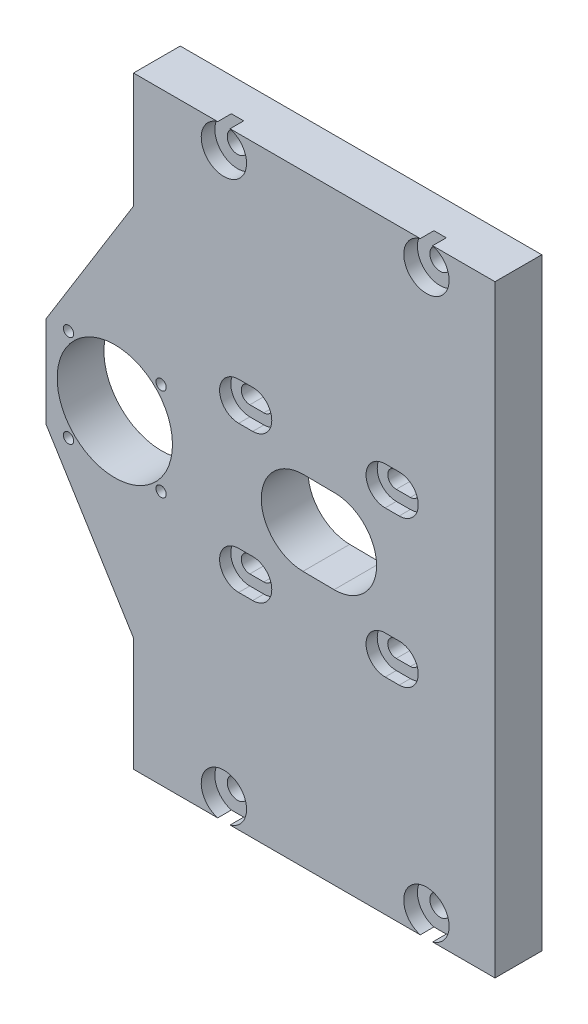
SolidWorks part; units mm, degrees
ref_plane "Front Plane" through (0, 0, 0) normal (0, 0, 1) x (1, 0, 0)
ref_plane "Top Plane" through (0, 0, 0) normal (0, 1, 0) x (1, 0, 0)
ref_plane "Right Plane" through (0, 0, 0) normal (1, 0, 0) x (0, 0, -1)
sketch "Sketch1" plane through (0, 0, 0) normal (0, 0, 1) x (1, 0, 0)
  line L24 (-148, 255) -> (-148, 190) construction
  line L31 (-148, 70) -> (-148, 10) construction
  line L32 (-148, 33.5) -> (-32, 33.5) construction
  line L36 (-32, 227) -> (-148, 227) construction
  line L37 (-148, 227) -> (-148, 190)
  line L38 (-148, 70) -> (-148, 33.5)
  line L39 (-148, 33.5) -> (-32, 33.5)
  line L43 (-32, 227) -> (-148, 227)
  line L44 (-176, 115.2267) -> (-176, 144.7733) construction
  line L45 (-176, 115.2267) -> (-176, 144.7733)
  line L46 (-176, 144.7733) -> (-148, 190)
  line L47 (-176, 115.2267) -> (-148, 70)
  line L51 (-32, 33.5) -> (-32, 227)
  circle A8 centre (-154, 130) radius 18.5
  circle A9 centre (-154, 130) radius 18.5
  dimension "D1" = 0.5
extrude "Boss-Extrude1" add sketch "Sketch1" along normal blind 15
sketch "Sketch2" plane through (0, 0, 15) normal (0, 0, 1) x (1, 0, 0)
  circle A1 centre (-139.1508, 115.1508) radius 2.25
  circle A3 centre (-168.8492, 115.1508) radius 2.25
  circle A5 centre (-168.8492, 144.8492) radius 2.25
  circle A7 centre (-139.1508, 144.8492) radius 2.25
hole_wizard "M4x0.7 Tapped Hole1" positions "Sketch3" profile "Sketch4" tap size "M4x0.7" standard "ANSI Metric"
sketch "Sketch3" plane through (0, 0, 15) normal (0, 0, 1) x (1, 0, 0)
  point P0 (-168.8492, 144.8492)
  point P3 (-139.1508, 144.8492)
  point P6 (-139.1508, 115.1508)
  point P9 (-168.8492, 115.1508)
sketch "Sketch4" plane through (-168.8492, 144.8492, 15) normal (1, 0, 0) x (0, -1, 0)
  line L0 (0, 0) -> (0, 14.1)
  line L1 (0, 14.1) -> (1.65, 13.1086)
  line L2 (1.65, 13.1086) -> (1.65, 0)
  line L5 (1.65, 0) -> (0, 0)
  line L10 (0, 14.1) -> (-1.65, 13.1086) construction
  line L11 (0, -6.35) -> (0, 107.95) construction
  dimension "Tap Drill Dia." = 3.3
  dimension "Tap Drill Depth" = 14.1
  dimension "Drill Angle" = 118
cosmetic thread "Hole Thread1"
cosmetic thread "Hole Thread2"
cosmetic thread "Hole Thread3"
cosmetic thread "Hole Thread4"
hole_wizard "CBORE for M6 Hex Head Bolt1" positions "Sketch5" profile "Sketch6" counterbore size "M6" standard "ANSI Metric"
sketch "Sketch5" plane through (0, 0, 15) normal (0, 0, 1) x (1, 0, 0)
  point P0 (-54, 220)
  point P3 (-119, 220)
  point P6 (-54, 40.5)
  point P9 (-119, 40.5)
sketch "Sketch6" plane through (-54, 220, 15) normal (1, 0, 0) x (0, -1, 0)
  line L0 (0, 0) -> (0, 29.9828)
  line L1 (0, 29.9828) -> (3.3, 28)
  line L2 (3.3, 28) -> (3.3, 4.38)
  line L3 (3.3, 4.38) -> (7.275, 4.38)
  line L4 (7.275, 4.38) -> (7.275, 0)
  line L5 (7.275, 0) -> (0, 0)
  line L10 (0, 29.9828) -> (-3.3, 28) construction
  line L11 (0, -6.35) -> (0, 107.95) construction
  dimension "Hole Dia." = 6.6
  dimension "Hole Depth" = 28
  dimension "C'Bore Dia." = 14.55
  dimension "C'Bore Depth" = 4.38
  dimension "Drill Angle" = 118
sketch "Sketch7" plane through (0, 0, 15) normal (0, 0, 1) x (1, 0, 0)
  line L0 (-83.5, 129.1439) -> (-88.5, 129.1439)
  line L1 (-107, 152.6439) -> (-112, 152.6439)
  line L2 (-60, 152.6439) -> (-65, 152.6439)
  line L3 (-60, 105.6439) -> (-65, 105.6439)
  line L4 (-107, 105.6439) -> (-112, 105.6439)
  circle A1 centre (-60, 105.6439) radius 2.85 construction
  circle A2 centre (-83.5, 129.1439) radius 13.5
  circle A3 centre (-83.5, 129.1439) radius 13.5
  circle A4 centre (-107, 105.6439) radius 2.85 construction
  circle A5 centre (-107, 152.6439) radius 2.85 construction
  circle A6 centre (-60, 152.6439) radius 2.85 construction
  circle A7 centre (-60, 105.6439) radius 2.85
  circle A8 centre (-107, 105.6439) radius 2.85
  circle A9 centre (-107, 152.6439) radius 2.85
  circle A10 centre (-60, 152.6439) radius 2.85
  dimension "D1" = 1
hole_wizard "Ø1.0mm Dowel Slot1" positions "Sketch8" profile "Sketch9" size "Ø1.0" standard "ANSI Metric" slot yes
sketch "Sketch8" plane through (0, 0, 15) normal (0, 0, 1) x (1, 0, 0)
  line L0 (-106.9991, 129.3233) -> (-70.0009, 128.9645) construction
  point P0 (-88.5, 129.1439)
  dimension "D1" = 37
sketch "Sketch9" plane through (-88.5, 129.1439, 15) normal (1, 0, 0) x (0, -1, 0)
  line L0 (0, 0) -> (0, 36.1116)
  line L1 (0, 36.1116) -> (13.5, 28)
  line L2 (13.5, 28) -> (13.5, 0)
  line L5 (13.5, 0) -> (0, 0)
  line L10 (0, 36.1116) -> (-13.5, 28) construction
  line L11 (0, -6.35) -> (0, 107.95) construction
  dimension "Hole Dia." = 27
  dimension "Hole Depth" = 28
  dimension "Drill Angle" = 118
hole_wizard "CBORE SLOT for M5 Hex Head Bolt1" positions "Sketch10" profile "Sketch11" size "M5" standard "ANSI Metric" slot yes
sketch "Sketch10" plane through (0, 0, 15) normal (0, 0, 1) x (1, 0, 0)
  line L0 (-117, 152.6439) -> (-107, 152.6439) construction
  point P0 (-112, 152.6439)
  point P5 (-112, 105.6439)
  point P8 (-65, 152.6439)
  point P11 (-65, 105.6439)
  dimension "D1" = 10
sketch "Sketch11" plane through (-112, 152.6439, 15) normal (1, 0, 0) x (0, -1, 0)
  line L0 (0, 0) -> (0, 29.6524)
  line L1 (0, 29.6524) -> (2.75, 28)
  line L2 (2.75, 28) -> (2.75, 3.58)
  line L3 (2.75, 3.58) -> (6.12, 3.58)
  line L4 (6.12, 3.58) -> (6.12, 0)
  line L5 (6.12, 0) -> (0, 0)
  line L10 (0, 29.6524) -> (-2.75, 28) construction
  line L11 (0, -6.35) -> (0, 107.95) construction
  dimension "Hole Dia." = 5.5
  dimension "Hole Depth" = 28
  dimension "C'Bore Dia." = 12.24
  dimension "C'Bore Depth" = 3.58
  dimension "Drill Angle" = 118
